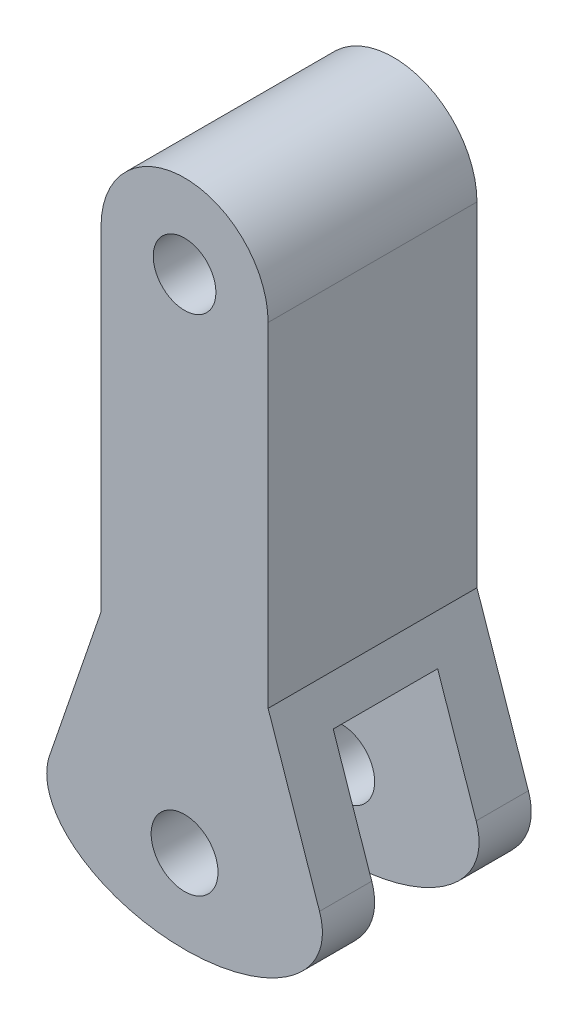
SolidWorks part; units mm, degrees
ref_plane "前视基准面" through (0, 0, 0) normal (0, 0, 1) x (1, 0, 0)
ref_plane "上视基准面" through (0, 0, 0) normal (0, 1, 0) x (1, 0, 0)
ref_plane "右视基准面" through (0, 0, 0) normal (1, 0, 0) x (0, 0, -1)
sketch "草图1" plane through (0, 0, 0) normal (0, 0, 1) x (1, 0, 0)
  line L0 (-20, -80) -> (-32.3109, -115.934)
  line L1 (-20, 0) -> (20, 0)
  line L2 (-20, 0) -> (-20, -120)
  line L3 (-20, -120) -> (20, -120)
  line L4 (20, 0) -> (20, -120)
  line L5 (-20, -80) -> (20, -80) construction
  line L6 (0, -80) -> (0, -154.1436) construction
  line L7 (20, -80) -> (32.3109, -115.934)
  circle A0 centre (0, 0) radius 20
  circle A1 centre (0, -120) radius 20
  ellipse E0 centre (0, -120) end of major axis (-33, -120) minor radius 20
  point P19 (0, -140.2359)
  point P20 (0, -140.2359)
  point P21 (0, 0)
  point P22 (0, 0)
  dimension "D1" = 40
  dimension "D2" = 120
  dimension "D3" = 40
  dimension "D4" = 33
extrude "凸台-拉伸1" add sketch "草图1" along normal blind 50 contours E0 L4 A0 L2 | E0 L2 L0 | L2 E0 A1 | A1 E0 L2 | L4 E0 A1 | E0 L7 L4 | E0 L4 A1 | L1 A0 | L1 A0 | L3 A1 | L3 A1 | A1 region at (-23.6834, -98.5266, 0) region at (0, -58.3973, 0) region at (-23.656, -122.4198, 0) region at (0, 8.4883, 0) region at (0, -8.4883, 0) region at (-15.7177, -105.8901, 0) region at (0, -111.5117, 0) region at (0, -128.4883, 0) region at (15.7177, -105.8901, 0) region at (23.656, -122.4198, 0) region at (23.6834, -98.5266, 0)
sketch "草图2" plane through (20, 0, 0) normal (1, 0, 0) x (0, 0, -1)
  line L0 (-25, -80) -> (-25, -164.4758) construction
  line L1 (-50, -80) -> (0, -80) construction
  line L2 (-37.5, -89) -> (-37.5, -150.4701)
  line L3 (-37.5, -89) -> (-12.5, -89)
  line L4 (-37.5, -150.4701) -> (-12.5, -150.4701)
  line L5 (-12.5, -89) -> (-12.5, -150.4701)
  line L6 (-37.5, -89) -> (-12.5, -150.4701) construction
  line L7 (-37.5, -150.4701) -> (-12.5, -89) construction
  point P4 (-31.8417, -87.5512)
  point P5 (-25, -119.7351)
  point P6 (-25, -118.5171)
  point P7 (-21.2055, -88.9019)
  dimension "D1" = 9
  dimension "D2" = 25
extrude "切除-拉伸1" cut sketch "草图2" against normal through all both and the other way through all
sketch "草图3" plane through (0, 0, 50) normal (0, 0, 1) x (1, 0, 0)
  line L4 (32.3109, -115.934) -> (20, -80)
  line L5 (20, -80) -> (20, 0)
  line L6 (-20, 0) -> (-20, -80)
  line L7 (-20, -80) -> (-32.3109, -115.934)
  line L8 (32.3109, -115.934) -> (20, -80)
  line L9 (20, -80) -> (20, 0)
  line L10 (-20, 0) -> (-20, -80)
  line L11 (-20, -80) -> (-32.3109, -115.934)
  circle A0 centre (0, -120) radius 8
  arc A1 (20, 0) -> (-20, 0) centre (0, 0) ccw
  arc A2 (20, 0) -> (-20, 0) centre (0, 0) ccw
  ellipse E1 centre (0, -120) end of major axis (-33, -120) minor radius 20 (-32.3109, -115.934) -> (32.3109, -115.934) ccw
  ellipse E2 centre (0, -120) end of major axis (-33, -120) minor radius 20 (-32.3109, -115.934) -> (32.3109, -115.934) ccw
  dimension "D2" = 16
  dimension "D1" = 0
extrude "切除-拉伸2" cut sketch "草图3" against normal through all both and the other way through all flip side to cut
sketch "草图4" plane through (0, 0, 50) normal (0, 0, 1) x (1, 0, 0)
  circle A0 centre (0, 0) radius 7.5
  dimension "D1" = 15
extrude "切除-拉伸3" cut sketch "草图4" against normal through all
